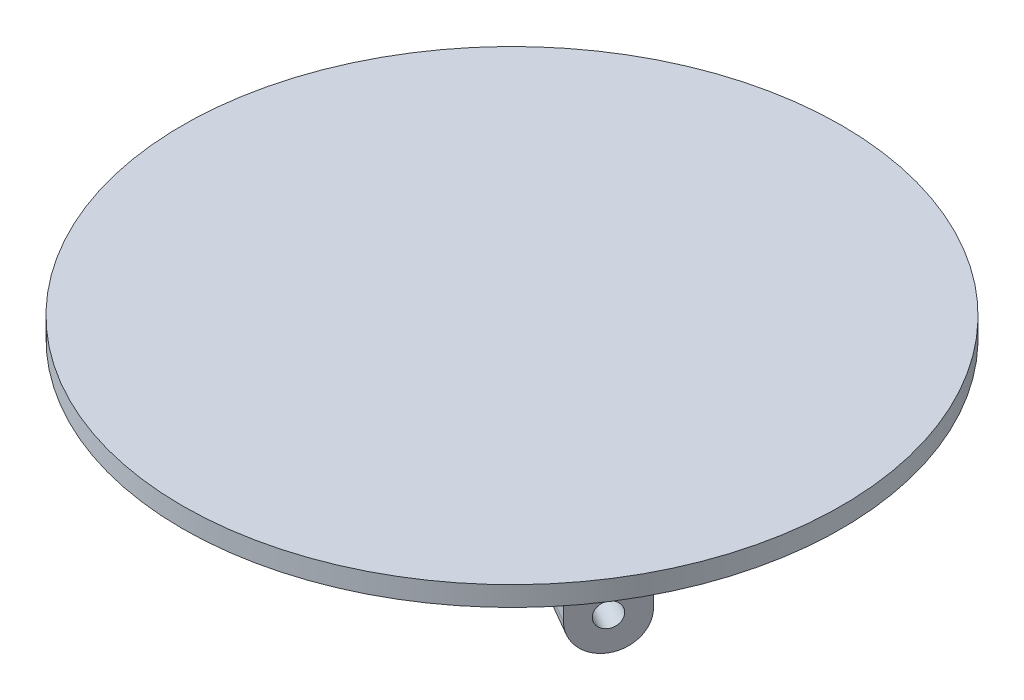
SolidWorks part; units mm, degrees
ref_plane "Front Plane" through (0, 0, 0) normal (0, 0, 1) x (1, 0, 0)
ref_plane "Top Plane" through (0, 0, 0) normal (0, 1, 0) x (1, 0, 0)
ref_plane "Right Plane" through (0, 0, 0) normal (1, 0, 0) x (0, 0, -1)
sketch "Sketch2" plane through (0, 0, 0) normal (0, 1, 0) x (1, 0, 0)
  line L0 (0, 0) -> (-5, 2.8868)
  line L4 (-5, 2.8868) -> (-5, 40)
  line L5 (-5, 40) -> (5, 40)
  line L6 (5, 40) -> (5, 2.8868)
  line L7 (5, 2.8868) -> (0, 0)
  line L8 (0, 0) -> (0, 124.9609) construction
  dimension "D1" = 120
  dimension "D2" = 60
  dimension "D3" = 10
  dimension "D4" = 40
extrude "Boss-Extrude1" add sketch "Sketch2" along normal blind 17
sketch "Sketch3" plane through (5, 0, 0) normal (1, 0, 0) x (0, 0, -1)
  line L0 (40, 17) -> (40, 0) construction
  line L1 (0, 0) -> (35, 0)
  line L2 (0, 0) -> (0, 14)
  line L3 (0, 14) -> (35, 14)
  line L4 (35, 0) -> (35, 14)
  dimension "D1" = 14
  dimension "D3" = 5
extrude "Cut-Extrude1" cut sketch "Sketch3" against normal up to next
fillet "Fillet1" radius 5 2 edges at (-5, 0, -37.5) (5, 0, -37.5)
fillet "Fillet2" [suppressed] radius 3.4
sketch "Sketch4" plane through (0, 0, -40) normal (0, 0, -1) x (-1, 0, 0)
  circle A0 centre (0, 5) radius 1.7
  point P0 (0, 5)
  dimension "D1" = 3.4
hole_wizard "M3 Clearance Hole1" positions "Sketch4" profile "Sketch5" hole size "M3" standard "ANSI Metric" end condition up to next
sketch "Sketch5" plane through (0, 5, -40) normal (1, 0, 0) x (0, 1, 0)
  line L0 (0, 0) -> (0, 5)
  line L1 (0, 5) -> (1.8, 5)
  line L2 (1.8, 5) -> (1.8, 0)
  line L5 (1.8, 0) -> (0, 0)
  line L11 (0, -6.35) -> (0, 107.95) construction
  dimension "Thru Hole Dia." = 3.6
  dimension "Thru Hole Depth" = 5
pattern_circular "CirPattern1" count 3 over 360 about axis through (0, 17, 0) along (0, -1, 0) of "Boss-Extrude1", "Fillet1", "Fillet2", "Cut-Extrude1", "M3 Clearance Hole1" reverse direction yes
sketch "Sketch6" plane through (0, 14, 0) normal (0, 1, 0) x (1, 0, 0)
  circle A0 centre (0, 0) radius 50
  dimension "D1" = 100
extrude "Boss-Extrude2" add sketch "Sketch6" along normal up to surface (3 mm away) up to face at (0, 17, 0)
fillet "Fillet3" [suppressed] radius 10 type face fillet
fillet "Fillet4" [suppressed] radius 10 type face fillet
fillet "Fillet5" [suppressed] radius 10 type face fillet
fillet "Fillet6" radius 2 12 edges at (0, 14, -35) (5, 14, -37.5) (-5, 14, -37.5) (0, 14, -40) (-34.976, 14, 14.4199) (-30.3109, 14, 17.5) (-34.641, 14, 20) (-29.976, 14, 23.0801) (29.976, 14, 23.0801) (34.641, 14, 20) (30.3109, 14, 17.5) (34.976, 14, 14.4199)
